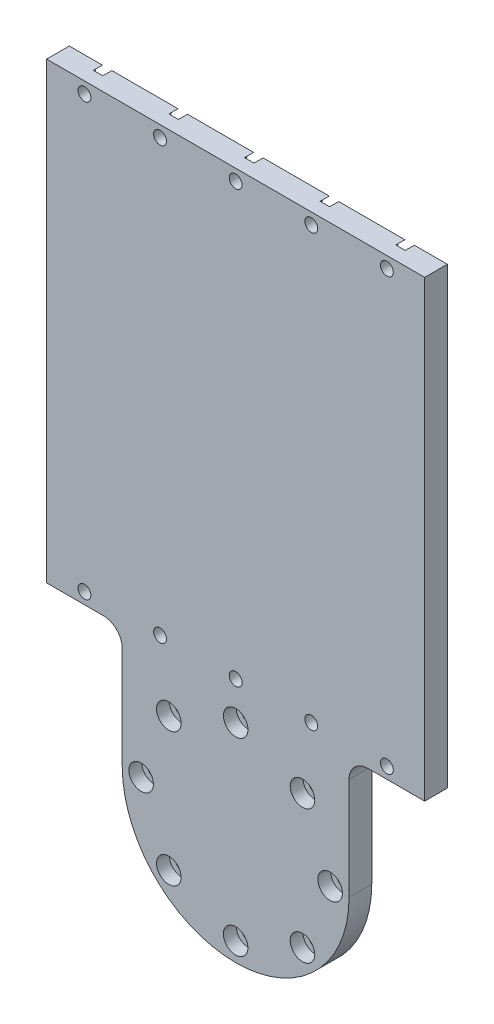
SolidWorks part; units mm, degrees
material "6061-T6 (SS)"
ref_plane "Front Plane" through (0, 0, 0) normal (0, 0, 1) x (1, 0, 0)
ref_plane "Top Plane" through (0, 0, 0) normal (0, 1, 0) x (1, 0, 0)
ref_plane "Right Plane" through (0, 0, 0) normal (1, 0, 0) x (0, 0, -1)
sketch "Sketch1" plane through (0, 0, 0) normal (0, 0, 1) x (1, 0, 0)
  line L0 (-30, 0) -> (-30, 152)
  line L1 (-30, 152) -> (30, 152)
  line L2 (30, 152) -> (30, 0)
  arc A0 (-30, 0) -> (30, 0) centre (0, 0) ccw
  dimension "D1" = 60
  dimension "D2" = 152
extrude "Boss-Extrude1" add sketch "Sketch1" along normal blind 6
sketch "Sketch7" plane through (0, 0, 6) normal (0, 0, 1) x (1, 0, 0)
  line L1 (30, 152) -> (50, 152)
  line L2 (30, 152) -> (30, 32)
  line L3 (30, 32) -> (50, 32)
  line L4 (50, 152) -> (50, 32)
  line L5 (-30, 152) -> (-50, 152)
  line L6 (-30, 152) -> (-30, 32)
  line L7 (-30, 32) -> (-50, 32)
  line L8 (-50, 152) -> (-50, 32)
  dimension "D1" = 100
  dimension "D2" = 32
extrude "Boss-Extrude2" add sketch "Sketch7" against normal up to surface (6 mm away) up to face at (0, 68.5, 0)
sketch "Sketch2" plane through (0, 0, 6) normal (0, 0, 1) x (1, 0, 0)
  circle A0 centre (0, 0) radius 25
  point P6 (0, 25)
  point P12 (17.6777, 17.6777)
  point P13 (25, 0)
  point P14 (17.6777, -17.6777)
  point P15 (0, -25)
  point P16 (-17.6777, -17.6777)
  point P17 (-25, 0)
  point P18 (-17.6777, 17.6777)
  dimension "D1" = 50
  dimension "D2" = 8
hole_wizard "CBORE for M3 Hex Socket Head Cap Screw1" positions "Sketch2" profile "Sketch3" counterbore size "M3" standard "DIN" end condition through all
sketch "Sketch3" plane through (-17.6777, 17.6777, 6) normal (1, 0, 0) x (0, -1, 0)
  line L0 (0, 0) -> (0, 6)
  line L1 (0, 6) -> (1.7, 6)
  line L3 (1.7, 6) -> (1.7, 3.4)
  line L4 (1.7, 3.4) -> (3.25, 3.4)
  line L5 (3.25, 3.4) -> (3.25, 0)
  line L7 (3.25, 0) -> (0, 0)
  line L11 (0, -6.35) -> (0, 107.95) construction
  dimension "Thru Hole Dia." = 3.4
  dimension "Thru Hole Depth" = 6
  dimension "C'Bore Dia." = 6.5
  dimension "C'Bore Depth" = 3.4
sketch "Sketch4" plane through (0, 0, 0) normal (0, 0, -1) x (-1, 0, 0)
  line L0 (-30, 35) -> (30, 35) construction
  line L1 (30, 32) -> (30, 0) construction
  line L2 (-30, 0) -> (-30, 32) construction
  line L3 (-50, 152) -> (50, 152) construction
  line L4 (0, 152) -> (0, 149) construction
  point P7 (0, 35)
  point P23 (20, 35)
  point P24 (40, 35)
  point P25 (0, 35)
  point P26 (20, 35)
  point P27 (-20, 35)
  point P28 (0, 35)
  point P29 (-20, 35)
  point P30 (-40, 35)
  point P46 (0, 149)
  point P59 (20, 149)
  point P60 (40, 149)
  point P61 (0, 149)
  point P62 (20, 149)
  point P63 (-20, 149)
  point P64 (0, 149)
  point P65 (-20, 149)
  point P66 (-40, 149)
  dimension "D1" = 35
  dimension "D5" = 3
  dimension "D4" = 3
  dimension "D6" = 3
  dimension "D3" = 3
  dimension "D2" = 3
hole_wizard "CBORE for M3 Hex Socket Thin Head Cap Screw1" positions "Sketch4" profile "Sketch6" counterbore size "M3" standard "DIN"
sketch "Sketch6" plane through (40, 149, 0) normal (1, 0, 0) x (0, 1, 0)
  line L0 (0, 0) -> (0, 11.0215)
  line L1 (0, 11.0215) -> (1.7, 10)
  line L2 (1.7, 10) -> (1.7, 2.4)
  line L3 (1.7, 2.4) -> (3.25, 2.4)
  line L4 (3.25, 2.4) -> (3.25, 0)
  line L5 (3.25, 0) -> (0, 0)
  line L10 (0, 11.0215) -> (-1.7, 10) construction
  line L11 (0, -6.35) -> (0, 107.95) construction
  dimension "Hole Dia." = 3.4
  dimension "Hole Depth" = 10
  dimension "C'Bore Dia." = 6.5
  dimension "C'Bore Depth" = 2.4
  dimension "Drill Angle" = 118
fillet "Fillet1" radius 5 2 edges at (30, 32, 3) (-30, 32, 3)
